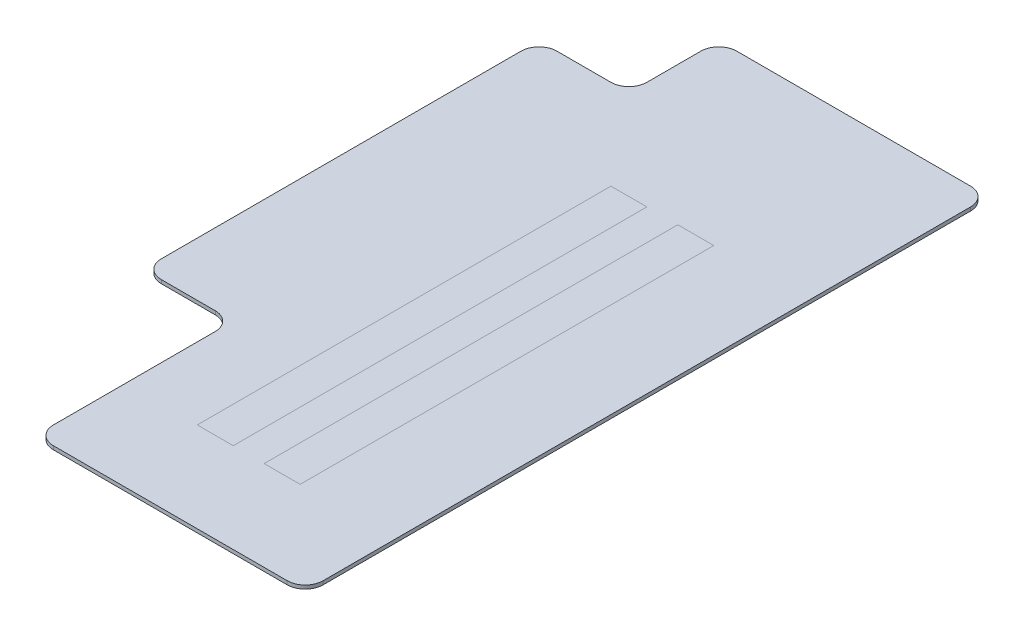
SolidWorks part; units mm, degrees
material "1.0116 (S235J2G3)"
ref_plane "Front Plane" through (0, 0, 0) normal (0, 0, 1) x (1, 0, 0)
ref_plane "Top Plane" through (0, 0, 0) normal (0, 1, 0) x (1, 0, 0)
ref_plane "Right Plane" through (0, 0, 0) normal (1, 0, 0) x (0, 0, -1)
sketch "Sketch2" plane through (0, 0, 0) normal (0, 1, 0) x (1, 0, 0)
  line L0 (-1000, 1600) -> (-1000, 600)
  line L1 (-950, 550) -> (-800, 550)
  line L2 (-750, 500) -> (-750, 50)
  line L3 (-700, 0) -> (-50, 0)
  line L4 (0, 50) -> (0, 1850)
  line L5 (-50, 1900) -> (-700, 1900)
  line L6 (-750, 1850) -> (-750, 1700)
  line L7 (-800, 1650) -> (-950, 1650)
  arc A0 (-50, 0) -> (0, 50) centre (-50, 50) ccw
  arc A1 (-750, 50) -> (-700, 0) centre (-700, 50) ccw
  arc A2 (-800, 550) -> (-750, 500) centre (-800, 500) cw
  arc A3 (-1000, 600) -> (-950, 550) centre (-950, 600) ccw
  arc A4 (-750, 1700) -> (-800, 1650) centre (-800, 1700) cw
  arc A5 (-1000, 1600) -> (-950, 1650) centre (-950, 1600) cw
  arc A6 (-700, 1900) -> (-750, 1850) centre (-700, 1850) ccw
  arc A7 (0, 1850) -> (-50, 1900) centre (-50, 1850) ccw
  point P11 (0, 0)
  point P16 (-750, 550)
  point P19 (-1000, 550)
  point P22 (-750, 1650)
  point P25 (-1000, 1650)
  point P28 (-750, 1900)
  dimension "D9" = 50
  dimension "D1" = 1000
  dimension "D2" = 1100
  dimension "D3" = 250
  dimension "D4" = 250
  dimension "D5" = 550
  dimension "D6" = 250
  dimension "D7" = 0
  dimension "D8" = 0
extrude "Boss-Extrude1" add sketch "Sketch2" along normal blind 10
sketch "Sketch3" plane through (0, 10, 0) normal (0, 1, 0) x (1, 0, 0)
  line L0 (-450, 1400) -> (-450, 250)
  line L1 (-450, 250) -> (-550, 250)
  line L2 (-550, 250) -> (-550, 1400)
  line L3 (-550, 1400) -> (-450, 1400)
  line L4 (-364, 250) -> (-364, 1400)
  line L5 (-364, 1400) -> (-264, 1400)
  line L6 (-264, 1400) -> (-264, 250)
  line L7 (-264, 250) -> (-364, 250)
  line L8 (-700, 0) -> (-50, 0) construction
  line L9 (-750, 500) -> (-750, 50) construction
  point P10 (-314, 250)
  dimension "D1" = 1150
  dimension "D2" = 1150
  dimension "D3" = 100
  dimension "D4" = 86
  dimension "D5" = 100
  dimension "D6" = 250
  dimension "D7" = 200
  dimension "D8" = 250
split line "Split Line1"
sketch "Sketch5" plane through (0, 0, 0) normal (0, -1, 0) x (1, 0, 0)
  line L0 (-930, -550) -> (-930, -1650)
  line L1 (-950, -550) -> (-800, -550) construction
  line L2 (-800, -1650) -> (-950, -1650) construction
  line L3 (-930, -1650) -> (-880, -1650)
  line L4 (-880, -1650) -> (-880, -550)
  line L5 (-1000, -1600) -> (-1000, -600) construction
  line L6 (-750, -434.7223) -> (-750, -376.9873)
  line L7 (-750, -500) -> (-750, -50) construction
  line L8 (-750, -376.9873) -> (0, -810)
  line L9 (0, -50) -> (0, -1850) construction
  line L10 (0, -810) -> (0, -867.735)
  line L11 (0, -867.735) -> (-750, -434.7223)
  line L17 (-700, 0) -> (-50, 0) construction
  line L24 (-750, -1775.2777) -> (0, -1342.265)
  line L25 (-750, -1850) -> (-750, -1700) construction
  line L26 (0, -1342.265) -> (0, -1400)
  line L27 (0, -1400) -> (-750, -1833.0127)
  line L28 (-750, -1833.0127) -> (-750, -1775.2777)
  line L29 (-50, -1900) -> (-700, -1900) construction
  dimension "D1" = 70
  dimension "D2" = 50
  dimension "D3" = 50
  dimension "D4" = 30
  dimension "D5" = 120
  dimension "D6" = 500
  dimension "D7" = 50
  dimension "D8" = 810
split line "Split Line2"
